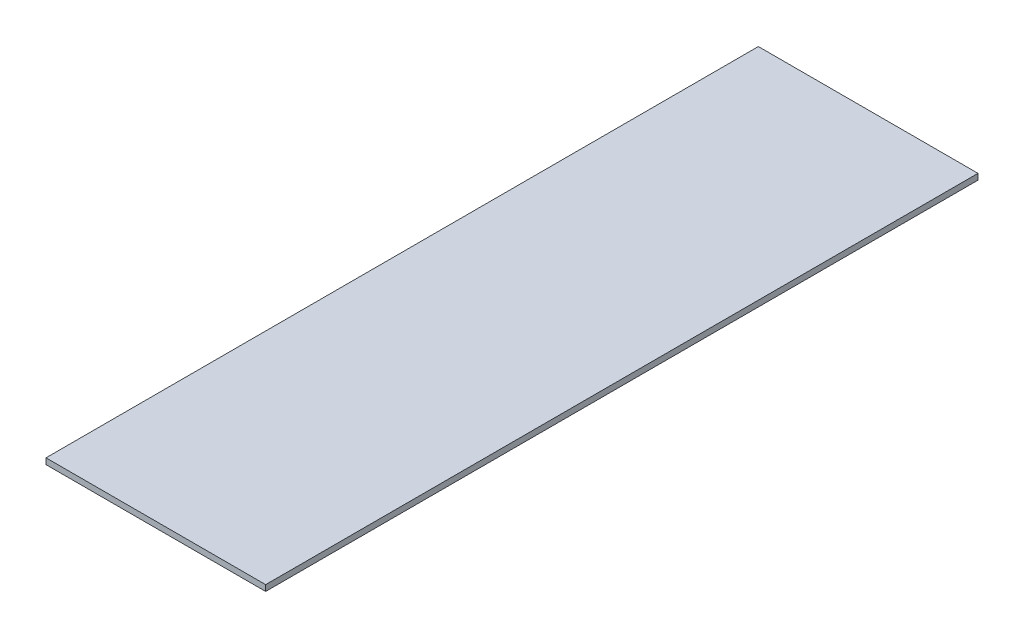
SolidWorks part; units mm, degrees
ref_plane "Front Plane" through (0, 0, 0) normal (0, 0, 1) x (1, 0, 0)
ref_plane "Top Plane" through (0, 0, 0) normal (0, 1, 0) x (1, 0, 0)
ref_plane "Right Plane" through (0, 0, 0) normal (1, 0, 0) x (0, 0, -1)
sketch "Sketch1" plane through (0, 0, 0) normal (0, 1, 0) x (1, 0, 0)
  line L1 (-117.475, 381) -> (117.475, 381)
  line L2 (-117.475, 381) -> (-117.475, -381)
  line L3 (-117.475, -381) -> (117.475, -381)
  line L4 (117.475, 381) -> (117.475, -381)
  line L5 (-117.475, 381) -> (117.475, -381) construction
  line L6 (-117.475, -381) -> (117.475, 381) construction
  point P0 (0, 0)
  dimension "D1" = 234.95
  dimension "D2" = 762
extrude "Boss-Extrude1" add sketch "Sketch1" along normal blind 3.175 and the other way blind 3.175
